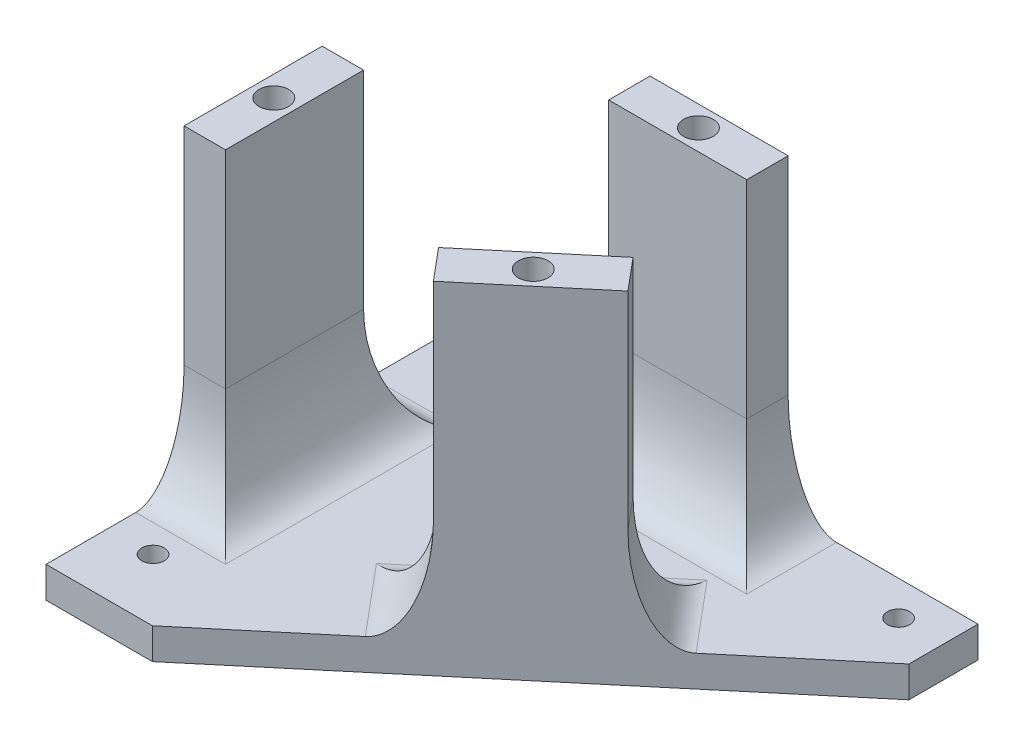
SolidWorks part; units mm, degrees
ref_plane "Front Plane" through (0, 0, 0) normal (0, 0, 1) x (1, 0, 0)
ref_plane "Top Plane" through (0, 0, 0) normal (0, 1, 0) x (1, 0, 0)
ref_plane "Right Plane" through (0, 0, 0) normal (1, 0, 0) x (0, 0, -1)
sketch "Sketch1" plane through (0, 0, 0) normal (0, 1, 0) x (1, 0, 0)
  line L0 (37.5, 60) -> (37.5, 18.5338) construction
  line L1 (15.4123, 0) -> (0, 0)
  line L2 (75, 50) -> (75, 60)
  line L3 (75, 60) -> (0, 60)
  line L4 (0, 0) -> (0, 60)
  line L5 (68.5, 55) -> (6.5, 55) construction
  line L6 (6.5, 55) -> (6.5, 9) construction
  line L7 (75, 50) -> (15.4123, 0)
  circle A0 centre (68.5, 55) radius 1.625
  circle A1 centre (6.5, 55) radius 1.625
  circle A2 centre (6.5, 9) radius 1.625
  dimension "D3" = 3.25
  dimension "D5" = 60
  dimension "D1" = 31
  dimension "D2" = 75
  dimension "D4" = 46
  dimension "D6" = 5
  dimension "D7" = 140
  dimension "D8" = 10
extrude "Boss-Extrude1" add sketch "Sketch1" along normal blind 4.5
sketch "Sketch2" plane through (0, 4.5, 0) normal (0, 1, 0) x (1, 0, 0)
  line L0 (75, 60) -> (0, 60) construction
  line L1 (47.5, 60) -> (27.5, 60)
  line L2 (47.5, 60) -> (47.5, 54)
  line L3 (47.5, 54) -> (27.5, 54)
  line L4 (27.5, 60) -> (27.5, 54)
  line L5 (0, 60) -> (0, 0) construction
  line L6 (0, 40) -> (6, 40)
  line L7 (0, 40) -> (0, 20)
  line L8 (0, 20) -> (6, 20)
  line L9 (6, 40) -> (6, 20)
  line L10 (52.8666, 31.4279) -> (37.5457, 18.5721)
  line L11 (15.4123, 0) -> (75, 50) construction
  line L12 (37.5457, 18.5721) -> (33.689, 23.1684)
  line L13 (33.689, 23.1684) -> (49.0099, 36.0241)
  line L14 (49.0099, 36.0241) -> (52.8666, 31.4279)
  point P18 (37.5, 60)
  point P19 (0, 30)
  point P20 (45.2062, 25)
  dimension "D1" = 6
  dimension "D2" = 6
  dimension "D3" = 6
  dimension "D4" = 20
  dimension "D5" = 20
  dimension "D6" = 20
extrude "Boss-Extrude2" add sketch "Sketch2" along normal blind 45
sketch "Sketch3" plane through (0, 49.5, 0) normal (0, 1, 0) x (1, 0, 0)
  line L1 (6, 20) -> (6, 40) construction
  line L2 (6, 40) -> (0, 40) construction
  line L3 (27.5, 54) -> (47.5, 54) construction
  line L4 (47.5, 54) -> (47.5, 60) construction
  line L5 (50.9382, 33.726) -> (35.6174, 20.8703) construction
  line L6 (52.8666, 31.4279) -> (49.0099, 36.0241) construction
  line L7 (33.689, 23.1684) -> (37.5457, 18.5721) construction
  circle A0 centre (3, 30) radius 2.15
  circle A1 centre (37.5, 57) radius 2.15
  circle A2 centre (43.2778, 27.2981) radius 2.15
  point P6 (43.2778, 27.2981)
  point P10 (6, 30)
  point P13 (3, 40)
  point P16 (37.5, 54)
  point P19 (47.5, 57)
  dimension "D1" = 4.3
extrude "Cut-Extrude1" cut sketch "Sketch3" against normal blind 5
fillet "Fillet1" radius 7 9 edges at (50.9382, 4.5, -33.726) (3, 4.5, -40) (35.6174, 4.5, -20.8703) (3, 4.5, -20) (27.5, 4.5, -57) (47.5, 4.5, -57) (41.3494, 4.5, -29.5963) (37.5, 4.5, -54) (6, 4.5, -30) second distance 15 first distance on face at (6.5, 4.5, -56.625)
